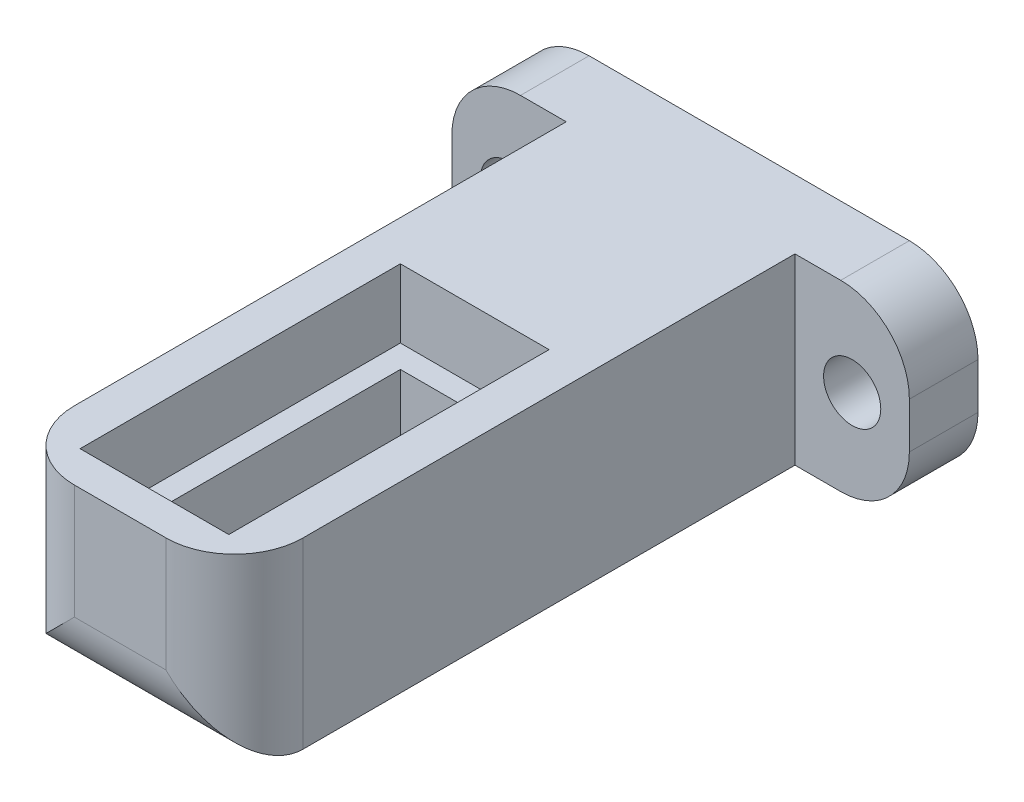
SolidWorks part; units mm, degrees
ref_plane "Plano frontal" through (0, 0, 0) normal (0, 0, 1) x (1, 0, 0)
ref_plane "Plano superior" through (0, 0, 0) normal (0, 1, 0) x (1, 0, 0)
ref_plane "Plano direito" through (0, 0, 0) normal (1, 0, 0) x (0, 0, -1)
sketch "Esboço1" plane through (0, 0, 0) normal (0, 1, 0) x (1, 0, 0)
  line L1 (-5, -13.75) -> (5, -13.75)
  line L2 (-5, -13.75) -> (-5, 13.75)
  line L3 (-5, 13.75) -> (5, 13.75)
  line L4 (5, -13.75) -> (5, 13.75)
  line L5 (-5, -13.75) -> (5, 13.75) construction
  line L6 (-5, 13.75) -> (5, -13.75) construction
  point P0 (0, 0)
  dimension "D1" = 10
  dimension "D2" = 27.5
extrude "Ressalto-extrusão1" add sketch "Esboço1" along normal blind 8
sketch "Esboço2" plane through (0, 8, 0) normal (0, 1, 0) x (1, 0, 0)
  line L0 (-5, -13.75) -> (5, -13.75) construction
  line L1 (-3.25, 1.75) -> (3.25, 1.75)
  line L2 (-3.25, 1.75) -> (-3.25, -12.25)
  line L3 (-3.25, -12.25) -> (3.25, -12.25)
  line L4 (3.25, 1.75) -> (3.25, -12.25)
  point P4 (0, -12.25)
  point P7 (0, -13.75)
  dimension "D1" = 0
  dimension "D2" = 6.5
  dimension "D3" = 14
  dimension "D4" = 1.5
extrude "Corte-extrusão1" cut sketch "Esboço2" against normal blind 3
sketch "Esboço3" plane through (0, 0, -13.75) normal (0, 0, -1) x (-1, 0, 0)
  line L1 (-5, 8) -> (-10, 8)
  line L2 (-5, 8) -> (-5, 0)
  line L3 (-5, 0) -> (-10, 0)
  line L4 (-10, 8) -> (-10, 0)
  dimension "D1" = 5
extrude "Ressalto-extrusão2" add sketch "Esboço3" against normal blind 3
sketch "Esboço5" plane through (0, 0, -10.75) normal (0, 0, 1) x (1, 0, 0)
  line L0 (5, 8) -> (10, 8) construction
  circle A0 centre (7.5, 4) radius 1.25
  point P4 (7.5, 8)
  dimension "D1" = 2.5
  dimension "D2" = 0
extrude "Corte-extrusão2" cut sketch "Esboço5" against normal through all
fillet "Filete1" radius 3 2 edges at (10, 0, -12.25) (10, 8, -12.25)
mirror "Espelhar3" about plane through (0, 0, 0) normal (1, 0, 0) of "Ressalto-extrusão2", "Filete1", "Corte-extrusão2"
sketch "Esboço6" plane through (0, 5, 0) normal (0, 1, 0) x (1, 0, 0)
  line L8 (-2.25, 0.75) -> (-2.25, -11.25)
  line L9 (-2.25, -11.25) -> (2.25, -11.25)
  line L10 (2.25, -11.25) -> (2.25, 0.75)
  line L11 (2.25, 0.75) -> (-2.25, 0.75)
  line L12 (-2.25, 0.75) -> (-2.25, -11.25)
  line L13 (-2.25, -11.25) -> (2.25, -11.25)
  line L14 (2.25, -11.25) -> (2.25, 0.75)
  line L15 (2.25, 0.75) -> (-2.25, 0.75)
  dimension "D1" = 1
extrude "Corte-extrusão3" cut sketch "Esboço6" against normal blind 3
sketch "Esboço7" plane through (0, 2, 0) normal (0, 1, 0) x (1, 0, 0)
  line L0 (2.25, 0.75) -> (-2.25, 0.75) construction
  circle A0 centre (0, -2.25) radius 2
  dimension "D1" = 4
  dimension "D2" = 3
extrude "Corte-extrusão4" cut sketch "Esboço7" against normal through all
fillet "Filete2" radius 3 3 edges at (5, 4, 13.75) (-5, 4, 13.75) (0, 0, 13.75)
